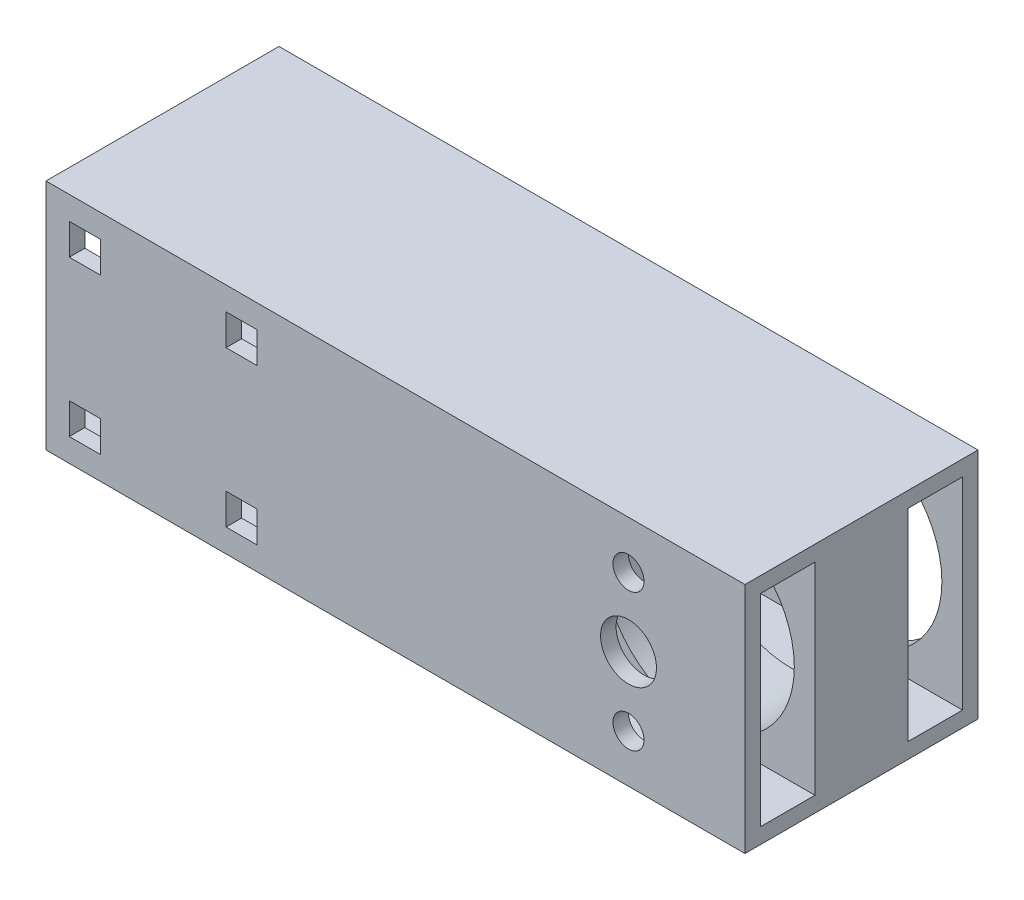
SolidWorks part; units mm, degrees
ref_plane "Front Plane" through (0, 0, 0) normal (0, 0, 1) x (1, 0, 0)
ref_plane "Top Plane" through (0, 0, 0) normal (0, 1, 0) x (1, 0, 0)
ref_plane "Right Plane" through (0, 0, 0) normal (1, 0, 0) x (0, 0, -1)
sketch "Sketch1" plane through (0, 0, 0) normal (1, 0, 0) x (0, 0, -1)
  line L1 (-15, -15) -> (15, -15)
  line L2 (-15, -15) -> (-15, 15)
  line L3 (-15, 15) -> (15, 15)
  line L4 (15, -15) -> (15, 15)
  line L5 (-15, -15) -> (15, 15) construction
  line L6 (-15, 15) -> (15, -15) construction
  line L11 (-5.1844, 5.1844) -> (5.1844, -5.1844) construction
  line L12 (-5.1844, -5.1844) -> (5.1844, 5.1844) construction
  line L13 (-13, 13) -> (-6, 13)
  line L14 (-13, 13) -> (-13, -13)
  line L15 (-13, -13) -> (-6, -13)
  line L16 (-6, 13) -> (-6, -13)
  line L17 (13, 13) -> (6, 13)
  line L18 (13, 13) -> (13, -13)
  line L19 (13, -13) -> (6, -13)
  line L20 (6, 13) -> (6, -13)
  point P0 (0, 0)
  point P7 (0, 0)
  dimension "D1" = 30
  dimension "D2" = 30
  dimension "D3" = 2
  dimension "D4" = 7
  dimension "D5" = 2
  dimension "D6" = 7
  dimension "D7" = 2
  dimension "D8" = 2
extrude "Boss-Extrude3" add sketch "Sketch1" along normal blind 90
sketch "Sketch6" plane through (0, 0, -15) normal (0, 0, -1) x (-1, 0, 0)
  line L0 (-90, -15) -> (-90, 15) construction
  circle A0 centre (-75, 0) radius 12.35
  dimension "D2" = 24.7
  dimension "D1" = 15
extrude "Cut-Extrude5" cut sketch "Sketch6" against normal blind 23
sketch "Sketch8" plane through (0, 0, 15) normal (0, 0, 1) x (1, 0, 0)
  line L0 (90, 15) -> (90, -15) construction
  circle A0 centre (75, 0) radius 3.6
  circle A1 centre (75, 8.85) radius 2
  circle A2 centre (75, -8.85) radius 2
  dimension "D2" = 7.2
  dimension "D5" = 4
  dimension "D6" = 4
  dimension "D1" = 15
  dimension "D3" = 8.85
  dimension "D4" = 8.85
extrude "Cut-Extrude6" cut sketch "Sketch8" against normal blind 17
sketch "Sketch9" plane through (0, 0, 0) normal (-1, 0, 0) x (0, 0, 1)
  line L0 (-6, 13) -> (6, 13)
  line L1 (-6, -13) -> (6, -13)
  line L2 (-6, 13) -> (-6, -13)
  line L3 (6, 13) -> (6, -13)
extrude "Cut-Extrude7" cut sketch "Sketch9" against normal blind 59
sketch "Sketch10" plane through (0, 0, -15) normal (0, 0, -1) x (-1, 0, 0)
  line L0 (0, 15) -> (-30.1838, 15)
  line L1 (-90, 15) -> (0, 15) construction
  line L2 (-30.1838, 15) -> (-30.1838, -15)
  line L3 (-90, -15) -> (0, -15) construction
  line L4 (-30.1838, -15) -> (0, -15)
  line L5 (-25.1838, 10) -> (0, 10)
  line L6 (0, -15) -> (0, 15) construction
  line L7 (-25.1838, 10) -> (-25.1838, -15)
  line L8 (-25.1919, 12.9939) -> (-22.5032, 11.6631) construction
  line L9 (-3, 8) -> (-7, 8)
  line L10 (-3, 8) -> (-3, 12)
  line L11 (-3, 12) -> (-7, 12)
  line L12 (-7, 8) -> (-7, 12)
  line L13 (-3, 8) -> (-7, 12) construction
  line L14 (-3, 12) -> (-7, 8) construction
  line L15 (-27.1838, 8) -> (-23.1838, 8)
  line L16 (-27.1838, 8) -> (-27.1838, 12)
  line L17 (-27.1838, 12) -> (-23.1838, 12)
  line L18 (-23.1838, 8) -> (-23.1838, 12)
  line L19 (-27.1838, 8) -> (-23.1838, 12) construction
  line L20 (-27.1838, 12) -> (-23.1838, 8) construction
  line L22 (-27.1838, -12) -> (-23.1838, -12)
  line L23 (-27.1838, -12) -> (-27.1838, -8)
  line L24 (-27.1838, -8) -> (-23.1838, -8)
  line L25 (-23.1838, -12) -> (-23.1838, -8)
  line L26 (-27.1838, -12) -> (-23.1838, -8) construction
  line L27 (-27.1838, -8) -> (-23.1838, -12) construction
  line L28 (-3, -12) -> (-7, -12)
  line L29 (-3, -12) -> (-3, -8)
  line L30 (-3, -8) -> (-7, -8)
  line L31 (-7, -12) -> (-7, -8)
  line L32 (-3, -12) -> (-7, -8) construction
  line L33 (-3, -8) -> (-7, -12) construction
  circle A0 centre (-25.1838, 10) radius 2
  circle A1 centre (-5, 10) radius 2
  circle A2 centre (-25.1838, -10) radius 2
  circle A3 centre (-5, -10) radius 2
  dimension "D3" = 4
  dimension "D4" = 5
  dimension "D5" = 4
  dimension "D7" = 4
  dimension "D8" = 4
  dimension "D1" = 5
  dimension "D2" = 5
  dimension "D6" = 5
  dimension "D9" = 4
  dimension "D10" = 4
  dimension "D11" = 4
  dimension "D12" = 4
  dimension "D13" = 4
extrude "Cut-Extrude8" cut sketch "Sketch10" against normal blind 34 contours L17 L18 L15 L16 | L11 L12 L9 L10 | L24 L25 L22 L23 | L30 L31 L28 L29
